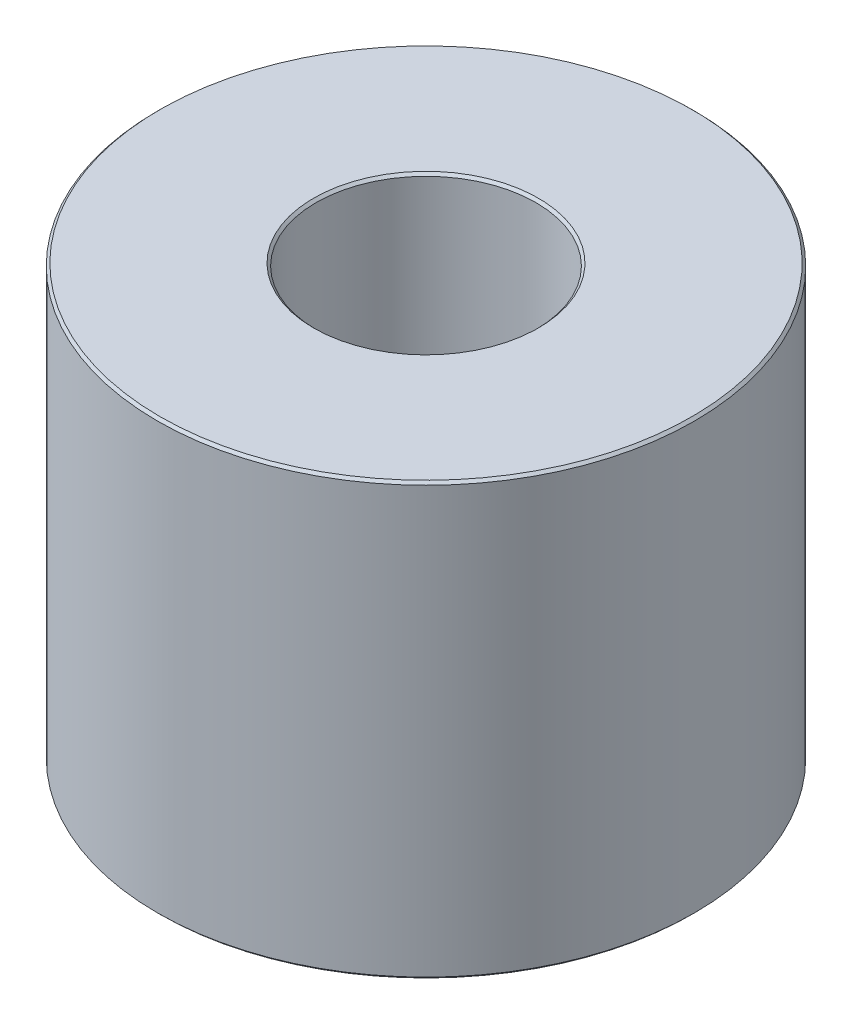
SolidWorks part; units mm, degrees
ref_plane "Front Plane" through (0, 0, 0) normal (0, 0, 1) x (1, 0, 0)
ref_plane "Top Plane" through (0, 0, 0) normal (0, 1, 0) x (1, 0, 0)
ref_plane "Right Plane" through (0, 0, 0) normal (1, 0, 0) x (0, 0, -1)
sketch "Sketch1" plane through (0, 0, 0) normal (0, 1, 0) x (1, 0, 0)
  circle A0 centre (0, 0) radius 52.5
  dimension "SLEEVE_OD" = 105
extrude "Boss-Extrude1" add sketch "Sketch1" along normal blind 84.2794
sketch "Sketch2" plane through (0, 0, 0) normal (0, 1, 0) x (1, 0, 0)
  circle A0 centre (0, 0) radius 21.4904
  dimension "BORE_D" = 42.9807
extrude "Cut-Extrude1" cut sketch "Sketch2" along normal through all
chamfer "Chamfer1" distance 0.4955 angle 45 4 edges at (0, 84.2794, 21.4904) (0, 0, 21.4904) (0, 0, 52.5) (0, 84.2794, 52.5)
